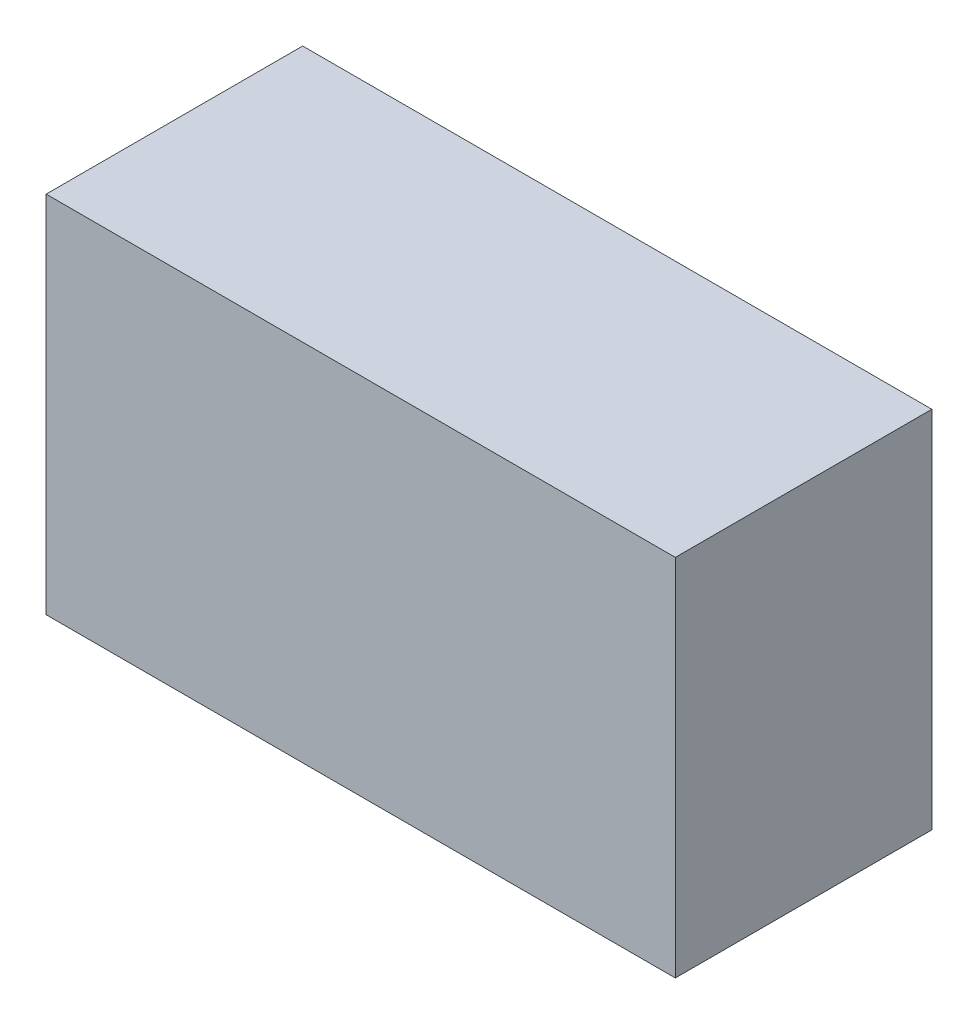
SolidWorks part; units mm, degrees
material "1060 Alloy"
ref_plane "Front" through (0, 0, 0) normal (0, 0, 1) x (1, 0, 0)
ref_plane "Top" through (0, 0, 0) normal (0, 1, 0) x (1, 0, 0)
ref_plane "Right" through (0, 0, 0) normal (1, 0, 0) x (0, 0, -1)
sketch "Sketch3" plane through (0, 0, 0) normal (0, 0, 1) x (1, 0, 0)
  line L0 (-0.127, -6.35) -> (30.1755, -6.35)
  line L1 (0, 0) -> (31.1484, 0)
  line L2 (0, 0) -> (0, -19.8376)
  line L3 (0, -19.8376) -> (31.1484, -19.8376)
  line L4 (31.1484, 0) -> (31.1484, -19.8376)
  line L5 (15.5742, -19.8376) -> (15.5742, 0) construction
  line L6 (15.5742, -6.35) -> (8.0621, -19.3614) construction
  line L15 (12.5496, -11.5887) -> (15.5742, -13.335) construction
  line L16 (15.5742, -6.35) -> (22.9274, -19.0862) construction
  circle A0 centre (15.5742, -6.35) radius 6.0492 construction
  point P14 (0, -6.35)
  point P17 (9.525, -6.35)
  point P19 (31.1484, -6.35)
  point P20 (7.7871, -19.8376)
  point P24 (23.3613, -19.8376)
  dimension "D2" = 6.35
  dimension "D6" = 3.4925
  dimension "D3" = 60
  dimension "D1" = 9.525
  dimension "D4" = 9.525
  dimension "D5" = 60
extrude "Boss-Extrude1" add sketch "Sketch3" along normal mid plane 12.7
sketch "Sketch4" plane through (0, 0, 0) normal (-1, 0, 0) x (0, 0, 1)
  circle A0 centre (0, -6.35) radius 3.175
  dimension "D1" = 6.35
extrude "Cut-Extrude1" cut sketch "Sketch4" against normal blind 9.525
ref_plane "Plane1" through (7.7871, -19.8376, 0) normal (-0.5, -0.866, 0) x (-0.866, 0.5, 0)
ref_plane "Mirror Plane" through (15.5742, 0, 0) normal (-1, 0, 0) x (0, 0, 1)
sketch "Sketch5" plane through (7.7871, -19.8376, 0) normal (-0.5, -0.866, 0) x (-0.866, 0.5, 0)
  circle A0 centre (0, 0) radius 3.175
  dimension "D1" = 6.35
extrude "Cut-Extrude5" cut sketch "Sketch5" against normal blind 9.525 and the other way up to next
sketch "Sketch6" plane through (0, 0, -6.35) normal (0, 0, -1) x (-1, 0, 0)
  circle A0 centre (-15.5742, -6.35) radius 3.175
  dimension "D1" = 6.35
extrude "Cut-Extrude6" cut sketch "Sketch6" against normal blind 9.525
mirror "Mirror1" about plane through (15.5742, 0, 0) normal (-1, 0, 0) of "Cut-Extrude5"
sketch "Sketch7" plane through (31.1484, 0, 0) normal (1, 0, 0) x (0, 0, -1)
  line L0 (6.35, -19.8376) -> (6.35, 0) construction
  line L1 (-6.35, -19.8376) -> (6.35, -19.8376)
  line L2 (-6.35, -19.8376) -> (-6.35, -18.034)
  line L3 (-6.35, -18.034) -> (6.35, -18.034)
  line L4 (6.35, -19.8376) -> (6.35, -18.034)
  line L5 (-6.35, 0) -> (6.35, 0) construction
  dimension "D1" = 18.034
extrude "Cut-Extrude7" cut sketch "Sketch7" against normal through all contours L3 L4 L1 L2
equation "\"truss_member_od\" = .25in"
equation "\"truss_member_id\"= 0in"
equation "\"truss_member_L1\" = 2.125in"
equation "\"connector_hole_depth\" = .375in"
equation "\"D1@Boss-Extrude1\"=\"truss_member_od\"*2"
equation "\"D6@Sketch3\"=\"truss_member_od\"/2*1.1"
equation "\"D1@Sketch4\"=\"truss_member_od\""
equation "\"D1@Cut-Extrude1\"=\"connector_hole_depth\""
equation "\"D1@Sketch3\"=\"connector_hole_depth\""
equation "\"D4@Sketch3\"=\"connector_hole_depth\""
equation "\"D1@Sketch5\"=\"truss_member_od\""
equation "\"D1@Cut-Extrude5\"=\"connector_hole_depth\""
equation "\"D1@Cut-Extrude6\"=\"connector_hole_depth\""
equation "\"D1@Sketch6\"=\"truss_member_od\""
